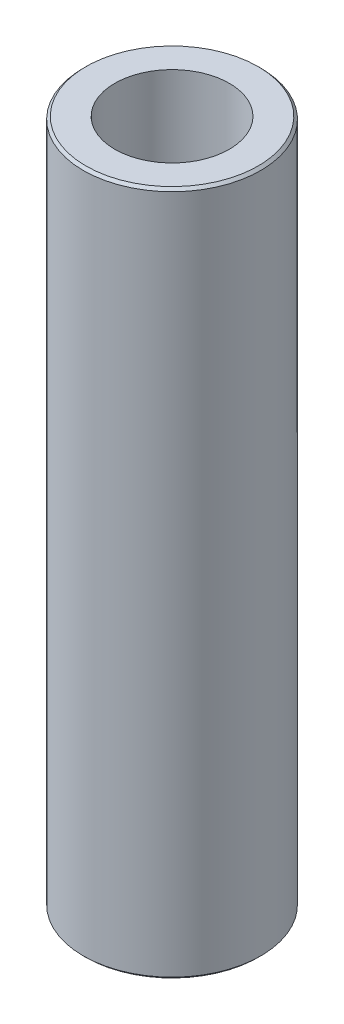
SolidWorks part; units mm, degrees
ref_plane "Front Plane" through (0, 0, 0) normal (0, 0, 1) x (1, 0, 0)
ref_plane "Top Plane" through (0, 0, 0) normal (0, 1, 0) x (1, 0, 0)
ref_plane "Right Plane" through (0, 0, 0) normal (1, 0, 0) x (0, 0, -1)
sketch "Sketch1" plane through (0, 0, 0) normal (0, 1, 0) x (1, 0, 0)
  circle A0 centre (0, 0) radius 15
  dimension "SHAFT_OD" = 30
extrude "Boss-Extrude1" add sketch "Sketch1" along normal blind 115.9166
sketch "Sketch2" plane through (0, 0, 0) normal (0, 1, 0) x (1, 0, 0)
  circle A0 centre (0, 0) radius 9.6802
  dimension "BORE_D" = 19.3604
extrude "Cut-Extrude1" cut sketch "Sketch2" along normal through all
chamfer "Chamfer1" distance 0.4449 angle 44.445 2 edges at (0, 115.9166, 15) (0, 0, 15) first distance on face at (0, 115.9166, 15) first distance on face at (0, 0, 9.6802)
